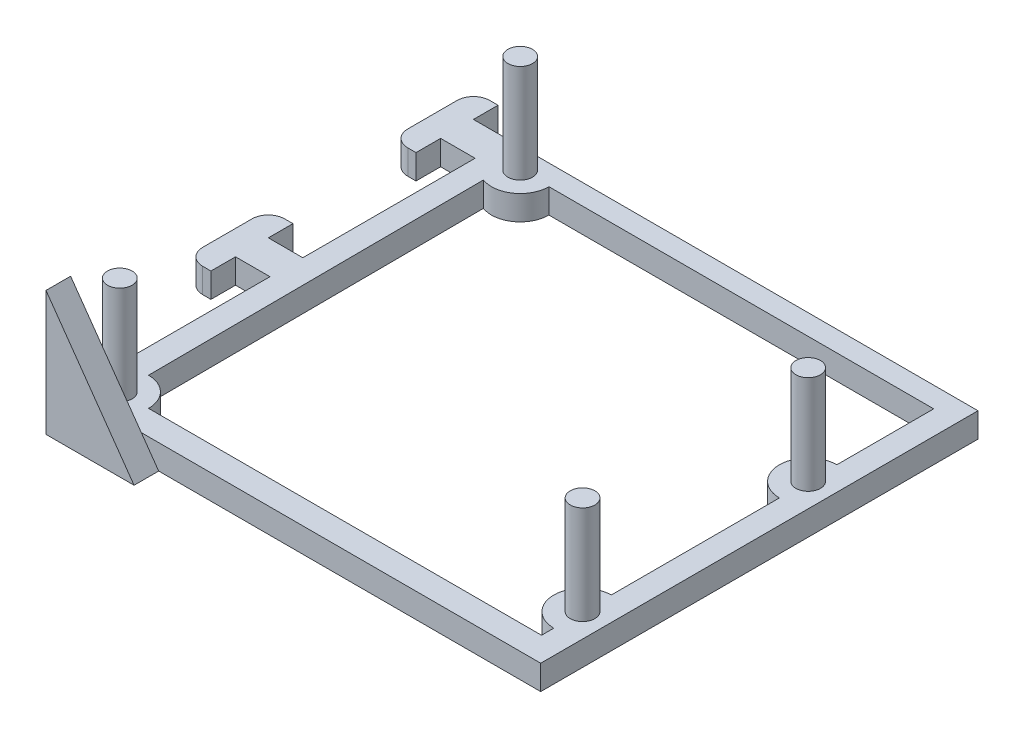
SolidWorks part; units mm, degrees
ref_plane "Front Plane" through (0, 0, 0) normal (0, 0, 1) x (1, 0, 0)
ref_plane "Top Plane" through (0, 0, 0) normal (0, 1, 0) x (1, 0, 0)
ref_plane "Right Plane" through (0, 0, 0) normal (1, 0, 0) x (0, 0, -1)
sketch "Sketch1" plane through (0, 0, 0) normal (0, 1, 0) x (1, 0, 0)
  line L0 (57.3, 5.3) -> (57.3, 0) construction
  line L1 (0, 0) -> (57.3, 0)
  line L2 (0, 0) -> (0, 51.3)
  line L3 (3, 6.5) -> (2.8, 47.5121)
  line L4 (7.5, 50.8) -> (54.4, 50.8)
  line L5 (57.3, 38.3) -> (57.3, 53.3) construction
  line L6 (0, 53.3) -> (57.3, 53.3)
  line L7 (57.3, 53.3) -> (57.3, 0)
  line L8 (54.4, 50.8) -> (54.4, 39)
  line L9 (54.4, 32) -> (54.4, 11.5)
  line L10 (6.5, 3) -> (54.4, 3)
  line L11 (54.4, 3) -> (54.4, 4.5)
  line L12 (2.8, 48.3) -> (2.8, 40.3) construction
  line L13 (0, 53.3) -> (-4.2, 53.3)
  line L14 (-4.2, 53.3) -> (-4.2, 56.3)
  line L15 (-4.2, 56.3) -> (-5.2, 56.3)
  line L16 (-7.2, 54.3) -> (-7.2, 48.3)
  line L17 (-7.2, 51.3) -> (0, 51.3) construction
  line L18 (0, 49.3) -> (-4.2, 49.3)
  line L19 (-4.2, 49.3) -> (-4.2, 46.3)
  line L20 (-4.2, 46.3) -> (-5.2, 46.3)
  line L21 (0, 53.3) -> (0, 51.3)
  circle A0 centre (4, 50.8) radius 1.5
  circle A1 centre (54.4, 35.5) radius 1.5
  circle A2 centre (54.4, 8) radius 1.5
  circle A3 centre (3, 3) radius 1.5
  arc A4 (-7.2, 54.3) -> (-5.2, 56.3) centre (-5.2, 54.3) cw
  arc A5 (2.8, 47.5121) -> (7.5, 50.8) centre (4, 50.8) ccw
  arc A6 (54.4, 39) -> (54.4, 32) centre (54.4, 35.5) ccw
  arc A7 (54.4, 11.5) -> (54.4, 4.5) centre (54.4, 8) ccw
  arc A8 (6.5, 3) -> (3, 6.5) centre (3, 3) ccw
  arc A9 (-7.2, 48.3) -> (-5.2, 46.3) centre (-5.2, 48.3) ccw
  point P42 (-7.2, 56.3)
  dimension "D1" = 3
  dimension "D2" = 3
  dimension "D3" = 3
  dimension "D4" = 3
  dimension "D5" = 4.2
  dimension "D6" = 7
  dimension "D7" = 7
  dimension "D8" = 7
  dimension "D12" = 2
  dimension "D9" = 3
  dimension "D10" = 3
  dimension "D11" = 5
extrude "Boss-Extrude1" add sketch "Sketch1" along normal blind 3 contours L6 L21 L2 L1 L7 A3 A2 A1 A0 L10 A8 L3 A5 L4 L8 A6 L9 A7 L11 region at (0.7826, 0, -24.65)
extrude "Boss-Extrude2" add sketch "Sketch1<3>" along normal blind 3 contours L16 A9 L20 L19 L18 L2 L21 L13 L14 L15 A4 region at (-4.3184, 0, -51.3)
sketch "Sketch1<3>" plane through (0, 0, 0) normal (0, 1, 0) x (1, 0, 0) same geometry as "Sketch1"
pattern_linear "LPattern1" count 2 spacing 25 along (0, 0, 1) of "Boss-Extrude2"
sketch "Sketch2" plane through (0, 0, 0) normal (0, 0, 1) x (1, 0, 0)
  line L0 (0, 0) -> (0, 15.2033)
  line L1 (0, 15.2033) -> (10.7358, 0)
  line L2 (0, 0) -> (57.3, 0) construction
  line L3 (0, 0) -> (10.7358, 0)
extrude "Boss-Extrude3" add sketch "Sketch2" along normal blind 3
extrude "Boss-Extrude4" add sketch "Sketch1<4>" along normal blind 15 contours A2 | A1 | A0 | A3 region at (54.4, 0, -35.5) region at (54.4, 0, -8)
sketch "Sketch1<4>" plane through (0, 0, 0) normal (0, 1, 0) x (1, 0, 0) same geometry as "Sketch1"
